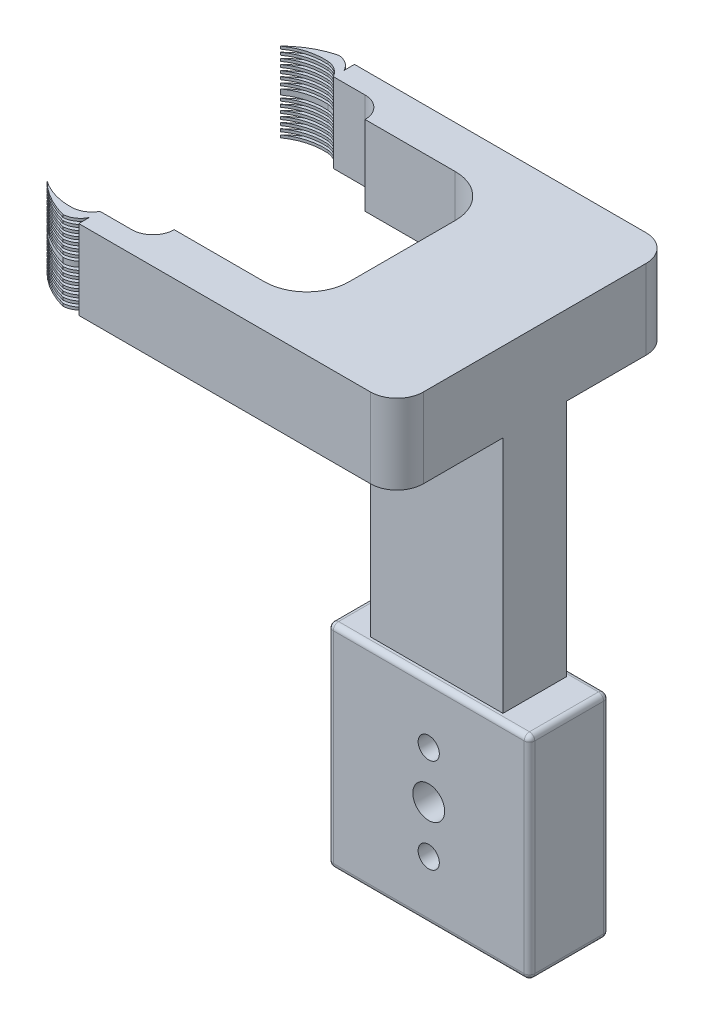
SolidWorks part; units mm, degrees
ref_plane "Front Plane" through (0, 0, 0) normal (0, 0, 1) x (1, 0, 0)
ref_plane "Top Plane" through (0, 0, 0) normal (0, 1, 0) x (1, 0, 0)
ref_plane "Right Plane" through (0, 0, 0) normal (1, 0, 0) x (0, 0, -1)
sketch "Sketch1" plane through (0, 0, 0) normal (0, 0, 1) x (1, 0, 0)
  line L1 (0, 0) -> (38, 0)
  line L2 (0, 0) -> (0, 40)
  line L3 (0, 40) -> (38, 40)
  line L4 (38, 0) -> (38, 40)
  dimension "D1" = 38
  dimension "D2" = 40
extrude "Boss-Extrude1" add sketch "Sketch1" along normal blind 15
sketch "Sketch2" plane through (0, 40, 0) normal (0, 1, 0) x (1, 0, 0)
  line L0 (19, 0) -> (19, -15) construction
  line L1 (38, 0) -> (0, 0) construction
  line L2 (38, -15) -> (0, -15) construction
  line L3 (0, -7.5) -> (38, -7.5) construction
  line L4 (0, -15) -> (0, 0) construction
  line L5 (38, -15) -> (38, 0) construction
  line L7 (6.5, -13.5) -> (31.5, -13.5)
  line L8 (6.5, -13.5) -> (6.5, -1.5)
  line L9 (6.5, -1.5) -> (31.5, -1.5)
  line L10 (31.5, -13.5) -> (31.5, -1.5)
  line L11 (6.5, -13.5) -> (31.5, -1.5) construction
  line L12 (6.5, -1.5) -> (31.5, -13.5) construction
  point P12 (19, -7.5)
  dimension "D1" = 25
  dimension "D2" = 12
extrude "Boss-Extrude2" add sketch "Sketch2" along normal blind 60
sketch "Sketch3" plane through (0, 0, 1.5) normal (0, 0, -1) x (-1, 0, 0)
  line L0 (-6.5, 100) -> (-6.5, 40) construction
  line L1 (-31.5, 100) -> (-6.5, 100)
  line L2 (-31.5, 100) -> (-31.5, 85)
  line L3 (-31.5, 85) -> (-6.5, 85)
  line L4 (-6.5, 100) -> (-6.5, 85)
  line L5 (-31.5, 40) -> (-6.5, 40) construction
  dimension "D1" = 45
extrude "Boss-Extrude3" add sketch "Sketch3" along normal blind 20
sketch "Sketch4" plane through (0, 0, 13.5) normal (0, 0, 1) x (1, 0, 0)
  line L0 (31.5, 100) -> (31.5, 40) construction
  line L1 (6.5, 100) -> (31.5, 100)
  line L2 (6.5, 100) -> (6.5, 85)
  line L3 (6.5, 85) -> (31.5, 85)
  line L4 (31.5, 100) -> (31.5, 85)
  line L5 (6.5, 40) -> (31.5, 40) construction
  dimension "D1" = 45
extrude "Boss-Extrude4" add sketch "Sketch4" along normal blind 20
sketch "Sketch5" plane through (6.5, 0, 0) normal (-1, 0, 0) x (0, 0, 1)
  line L0 (-18.5, 85) -> (1.5, 85) construction
  line L1 (-18.5, 100) -> (-10.5, 100)
  line L2 (-18.5, 100) -> (-18.5, 85)
  line L3 (-18.5, 85) -> (-10.5, 85)
  line L4 (-10.5, 100) -> (-10.5, 85)
  line L5 (33.5, 85) -> (13.5, 85) construction
  line L6 (33.5, 100) -> (25.5, 100)
  line L7 (33.5, 100) -> (33.5, 85)
  line L8 (33.5, 85) -> (25.5, 85)
  line L9 (25.5, 100) -> (25.5, 85)
  dimension "D1" = 8
  dimension "D2" = 8
extrude "Boss-Extrude5" add sketch "Sketch5" along normal blind 35
sketch "Sketch6" plane through (-28.5, 0, 0) normal (-1, 0, 0) x (0, 0, 1)
  line L0 (-18.5, 85) -> (-10.5, 85) construction
  line L1 (-10.5, 100) -> (-14.5, 100)
  line L2 (-10.5, 100) -> (-10.5, 85)
  line L3 (-10.5, 85) -> (-14.5, 85)
  line L4 (-14.5, 100) -> (-14.5, 85)
extrude "Cut-Extrude1" cut sketch "Sketch6" against normal blind 10
sketch "Sketch7" plane through (-28.5, 0, 0) normal (-1, 0, 0) x (0, 0, 1)
  line L0 (25.5, 85) -> (33.5, 85) construction
  line L1 (25.5, 100) -> (29.5, 100)
  line L2 (25.5, 100) -> (25.5, 85)
  line L3 (25.5, 85) -> (29.5, 85)
  line L4 (29.5, 100) -> (29.5, 85)
extrude "Cut-Extrude2" cut sketch "Sketch7" against normal blind 10
sketch "Sketch8" plane through (-28.5, 0, 0) normal (-1, 0, 0) x (0, 0, 1)
  line L1 (-18.5, 100) -> (-14.5, 100)
  line L2 (-18.5, 100) -> (-18.5, 85)
  line L3 (-18.5, 85) -> (-14.5, 85)
  line L4 (-14.5, 100) -> (-14.5, 85)
extrude "Boss-Extrude6" add sketch "Sketch8" along normal blind 10
sketch "Sketch9" plane through (0, 100, 0) normal (0, 1, 0) x (1, 0, 0)
  line L0 (-28.5, 18.5) -> (-28.5, 14.5) construction
  line L1 (-38.5, 14.5) -> (-38.5, 18.5) construction
  line L2 (-38.5, 16.5) -> (31.5, 16.5) construction
  line L3 (31.5, -33.5) -> (31.5, 18.5) construction
  line L4 (-38.5, 18.5) -> (31.5, 18.5) construction
  line L5 (-18.5, 14.5) -> (-38.5, 14.5) construction
  line L6 (-31.5, 18.5) -> (-31.5, 14.5) construction
  line L8 (-31.5, 18.5) -> (-38.5, 18.5)
  line L9 (-38.5, 18.5) -> (-38.5, 14.5)
  line L10 (-31.5, 18.5) -> (-28.5, 18.5)
  line L11 (-28.5, 18.5) -> (-28.5, 16.5)
  line L12 (-28.5, 14.5) -> (-38.5, 14.5)
  arc A0 (-28.5, 14.5) -> (-31.5, 16.5) centre (-31.8799, 12.6801) ccw
  arc A1 (-31.5, 16.5) -> (-38.5, 14.5) centre (-32.2043, 5.7151) ccw
  arc A2 (-28.5, 16.5) -> (-31.5, 18.5) centre (-31.6374, 15.0438) ccw
  arc A3 (-31.5, 18.5) -> (-38.5, 14.5) centre (-27.5546, 3.4706) ccw
  line M14 (31.5, 18.5) -> (-38.5, 18.5)
  line M15 (-38.5, 18.5) -> (-38.5, 14.5)
  line M16 (-38.5, 14.5) -> (-18.5, 14.5)
  dimension "D3" = 3.8387
  dimension "D4" = 3.4589
  dimension "D5" = 15.5386
  dimension "D6" = 10.8078
  dimension "D1" = 10
  dimension "D2" = 7
extrude "Cut-Extrude3" cut sketch "Sketch9" against normal through all contours A0 A1 M16 | A2 L11 M14 | A3 M14 M15 region at (-36.4402, 100, -17.2908) region at (-29.2284, 100, -17.9482) region at (-33.0932, 100, -15.3294)
sketch "Sketch11" plane through (0, 0, -18.5) normal (0, 0, -1) x (-1, 0, 0)
  line L0 (38.5, 92.5) -> (28.5, 92.5) construction
  line L1 (38.5, 85) -> (38.5, 100) construction
  line L2 (28.5, 85) -> (28.5, 100) construction
  line L3 (28.5, 99.5) -> (38.5, 99.5)
  line L4 (28.5, 85) -> (28.5, 100) construction
  line L5 (28.5, 99) -> (38.5, 99)
  line L6 (38.5, 100) -> (31.5, 100) construction
  line L7 (28.5, 98.5) -> (38.5, 98.5)
  line L8 (28.5, 98) -> (38.5, 98)
  line L9 (28.5, 97.5) -> (38.5, 97.5)
  line L10 (28.5, 97) -> (38.5, 97)
  line L11 (28.5, 96.5) -> (38.5, 96.5)
  line L12 (28.5, 96) -> (38.5, 96)
  line L13 (28.5, 95.5) -> (38.5, 95.5)
  line L14 (28.5, 95) -> (38.5, 95)
  line L15 (28.5, 94.5) -> (38.5, 94.5)
  line L16 (28.5, 94) -> (38.5, 94)
  line L17 (28.5, 93.5) -> (38.5, 93.5)
  line L18 (28.5, 93) -> (38.5, 93)
  line L19 (28.5, 92) -> (38.5, 92)
  line L20 (28.5, 91.5) -> (38.5, 91.5)
  line L21 (28.5, 91) -> (38.5, 91)
  line L22 (28.5, 90.5) -> (38.5, 90.5)
  line L23 (28.5, 90) -> (38.5, 90)
  line L24 (28.5, 89.5) -> (38.5, 89.5)
  line L25 (28.5, 89) -> (38.5, 89)
  line L26 (28.5, 88.5) -> (38.5, 88.5)
  line L27 (28.5, 88) -> (38.5, 88)
  line L28 (28.5, 87.5) -> (38.5, 87.5)
  line L29 (28.5, 87) -> (38.5, 87)
  line L30 (28.5, 86.5) -> (38.5, 86.5)
  line L31 (28.5, 86) -> (38.5, 86)
  line L32 (28.5, 85.5) -> (38.5, 85.5)
  line L33 (28.5, 99.5) -> (28.5, 99)
  line L34 (38.5, 99.5) -> (38.5, 99)
  line L35 (28.5, 98.5) -> (28.5, 98)
  line L36 (38.5, 98.5) -> (38.5, 98)
  line L37 (38.5, 97) -> (38.5, 96.5)
  line L38 (28.5, 97.5) -> (28.5, 97)
  line L39 (38.5, 97.5) -> (38.5, 97)
  line L40 (28.5, 96.5) -> (28.5, 96)
  line L41 (38.5, 96.5) -> (38.5, 96)
  line L42 (28.5, 95.5) -> (28.5, 95)
  line L43 (38.5, 95.5) -> (38.5, 95)
  line L44 (28.5, 94.5) -> (28.5, 94)
  line L45 (38.5, 94.5) -> (38.5, 94)
  line L46 (28.5, 93.5) -> (28.5, 93)
  line L47 (38.5, 93.5) -> (38.5, 93)
  line L48 (38.5, 85.5) -> (38.5, 86)
  line L49 (28.5, 85.5) -> (28.5, 86)
  line L50 (28.5, 86.5) -> (28.5, 87)
  line L51 (38.5, 86.5) -> (38.5, 87)
  line L52 (28.5, 87.5) -> (28.5, 88)
  line L53 (38.5, 87.5) -> (38.5, 88)
  line L54 (28.5, 88.5) -> (28.5, 89)
  line L55 (38.5, 88.5) -> (38.5, 89)
  line L56 (28.5, 89.5) -> (28.5, 90)
  line L57 (38.5, 89.5) -> (38.5, 90)
  line L58 (28.5, 90.5) -> (28.5, 91)
  line L59 (38.5, 90.5) -> (38.5, 91)
  line L60 (28.5, 91.5) -> (28.5, 92)
  line L61 (38.5, 91.5) -> (38.5, 92)
  dimension "D1" = 0.5
  dimension "D2" = 1
  dimension "D3" = 1.5
  dimension "D4" = 2
  dimension "D5" = 2.5
  dimension "D6" = 3
  dimension "D7" = 3.5
  dimension "D8" = 4
  dimension "D9" = 4.5
  dimension "D10" = 5
  dimension "D11" = 5.5
  dimension "D12" = 6
  dimension "D13" = 6.5
  dimension "D14" = 7
extrude "Cut-Extrude5" cut sketch "Sketch11" against normal through all contours L3 L34 L5 L33 | L7 L36 L8 L35 | L10 L38 L9 L39 | L41 L12 L40 L11 | L13 L43 L14 L42 | L15 L45 L16 L44 | L18 L47 L17 L46 | L20 L61 L19 L60 | L21 L59 L22 L58 | L23 L57 L24 L56 | L26 L55 L25 L54 | L28 L53 L27 L52 | L29 L51 L30 L50 | L32 L48 L31 L49
ref_plane "Plane1" through (0, 0, 7.5) normal (0, 0, 1) x (1, 0, 0)
mirror "Mirror3" about plane through (0, 0, 7.5) normal (0, 0, 1) of "Boss-Extrude6"
mirror "Mirror5" about plane through (0, 0, 7.5) normal (0, 0, 1) of "Cut-Extrude3"
mirror "Mirror6" about plane through (0, 0, 7.5) normal (0, 0, 1) of "Cut-Extrude5"
fillet "Fillet1" radius 8 1 edges at (6.5, 92.5, -10.5)
fillet "Fillet2" radius 8 1 edges at (6.5, 92.5, 25.5)
fillet "Fillet3" radius 4 1 edges at (-18.5, 92.5, 29.5)
fillet "Fillet4" radius 4 1 edges at (-18.5, 92.5, -14.5)
fillet "Fillet5" radius 5 2 edges at (31.5, 92.5, -18.5) (31.5, 92.5, 33.5)
fillet "Fillet6" radius 1 6 edges at (38, 0, 7.5) (19, 0, 15) (0, 40, 7.5) (19, 40, 0) (38, 40, 7.5) (19, 40, 15)
fillet "Fillet7" radius 1 8 edges at (0.2929, 39.7071, 14.7071) (0, 20, 15) (0, 0.2929, 14.7071) (37.7071, 39.7071, 0.2929) (38, 20, 0) (37.7071, 0.2929, 0) (0, 0, 7) (18.5, 0, 0)
fillet "Fillet8" radius 1 3 edges at (37.7071, 0.2929, 14.7071) (37.7071, 39.7071, 14.7071) (38, 20, 15)
fillet "Fillet9" radius 1 3 edges at (0.2929, 39.7071, 0.2929) (0.2929, 0.2929, 0.2929) (0, 20, 0)
sketch "Sketch15" plane through (0, 0, 0) normal (0, 0, -1) x (-1, 0, 0)
  line L0 (-19, 40) -> (-19, 0) construction
  line L1 (-37, 40) -> (-1, 40) construction
  line L2 (-1, 0) -> (-37, 0) construction
  line L3 (-38, 20) -> (0, 20) construction
  line L4 (-38, 1) -> (-38, 39) construction
  line L5 (0, 39) -> (0, 1) construction
  line L7 (-23.6127, 11.1033) -> (-14.3873, 11.1033)
  line L8 (-23.6127, 11.1033) -> (-23.6127, 28.8967)
  line L9 (-23.6127, 28.8967) -> (-14.3873, 28.8967)
  line L10 (-14.3873, 11.1033) -> (-14.3873, 28.8967)
  line L11 (-23.6127, 11.1033) -> (-14.3873, 28.8967) construction
  line L12 (-23.6127, 28.8967) -> (-14.3873, 11.1033) construction
  arc A0 (-14.3873, 28.8967) -> (-23.6127, 28.8967) centre (-19, 28.8967) ccw
  arc A1 (-14.3873, 11.1033) -> (-23.6127, 11.1033) centre (-19, 11.1033) cw
  point P12 (-19, 20)
  dimension "D1" = 9.2253
  dimension "D2" = 17.7933
extrude "Cut-Extrude7" cut sketch "Sketch15" against normal blind 5 contours L9 A0 | L7 L10 L9 L8 | A1 L7 region at (19, 20, 0) region at (19, 9.1456, 0) region at (19, 30.8544, 0)
sketch "Sketch16" plane through (0, 0, 5) normal (0, 0, -1) x (-1, 0, 0)
  line L0 (-19, 33.5093) -> (-19, 6.4907) construction
  line L1 (-23.6127, 20) -> (-14.3873, 20) construction
  line L2 (-23.6127, 11.1033) -> (-23.6127, 28.8967) construction
  line L3 (-14.3873, 11.1033) -> (-14.3873, 28.8967) construction
  arc A0 (-14.3873, 28.8967) -> (-23.6127, 28.8967) centre (-19, 28.8967) ccw construction
  arc A1 (-23.6127, 11.1033) -> (-14.3873, 11.1033) centre (-19, 11.1033) ccw construction
  circle A2 centre (-19, 28.8967) radius 2
  circle A3 centre (-19, 11.1033) radius 2
  circle A4 centre (-19, 20) radius 3
  dimension "D1" = 4
  dimension "D2" = 4
  dimension "D3" = 6
extrude "Cut-Extrude8" cut sketch "Sketch16" against normal through all contours A2 | A4 | A3
